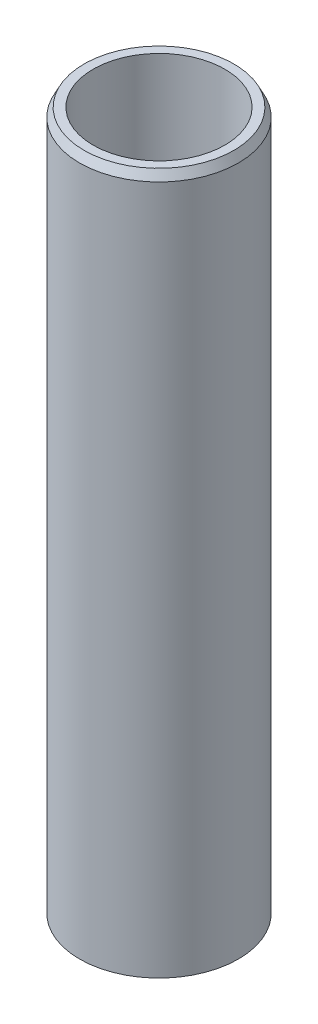
SolidWorks part; units mm, degrees
ref_plane "Front Plane" through (0, 0, 0) normal (0, 0, 1) x (1, 0, 0)
ref_plane "Top Plane" through (0, 0, 0) normal (0, 1, 0) x (1, 0, 0)
ref_plane "Right Plane" through (0, 0, 0) normal (1, 0, 0) x (0, 0, -1)
sketch "Sketch1" plane through (0, 0, 0) normal (0, 1, 0) x (1, 0, 0)
  circle A0 centre (0, 0) radius 27.5
  dimension "SHAFT_OD" = 55
extrude "Boss-Extrude1" add sketch "Sketch1" along normal blind 243.4344
sketch "Sketch2" plane through (0, 0, 0) normal (0, 1, 0) x (1, 0, 0)
  circle A0 centre (0, 0) radius 22.8126
  dimension "BORE_D" = 45.6252
extrude "Cut-Extrude1" cut sketch "Sketch2" along normal through all
chamfer "Chamfer1" distance 3.0184 angle 27.107 2 edges at (0, 243.4344, 27.5) (0, 0, 27.5) first distance on face at (0, 243.4344, 27.5) first distance on face at (0, 0, 22.8126)
